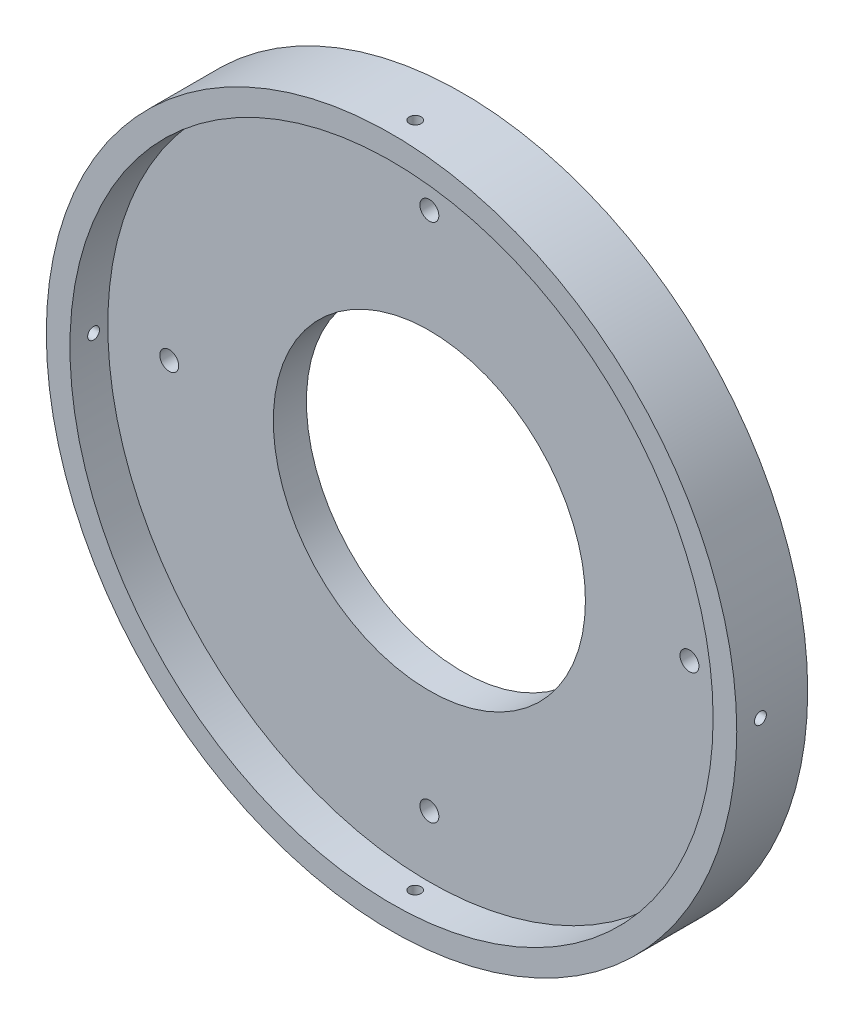
SolidWorks part; units mm, degrees
material "PET"
ref_plane "Front Plane" through (0, 0, 0) normal (0, 0, 1) x (1, 0, 0)
ref_plane "Top Plane" through (0, 0, 0) normal (0, 1, 0) x (1, 0, 0)
ref_plane "Right Plane" through (0, 0, 0) normal (1, 0, 0) x (0, 0, -1)
sketch "Sketch1" plane through (0, 0, 0) normal (0, 0, 1) x (1, 0, 0)
  circle A0 centre (0, 0) radius 73
  circle A1 centre (0, 0) radius 33
  dimension "D1" = 146
  dimension "D2" = 40
extrude "Boss-Extrude1" add sketch "Sketch1" along normal blind 7
sketch "Sketch2" plane through (0, 0, 7) normal (0, 0, 1) x (1, 0, 0)
  circle A0 centre (0, 0) radius 68
  circle A1 centre (0, 0) radius 73
  circle A2 centre (0, 0) radius 73
  dimension "D1" = 0
  dimension "D2" = 5
extrude "Boss-Extrude2" add sketch "Sketch2" along normal blind 8
sketch "Sketch3" plane through (0, 0, 0) normal (0, 1, 0) x (1, 0, 0)
  line L0 (-73, -15) -> (73, -15) construction
  circle A0 centre (0, -10) radius 1.25
  dimension "D2" = 2.5
  dimension "D1" = 5
extrude "Cut-Extrude1" cut sketch "Sketch3" against normal up to surface (73 mm away) up to face at (73, 0, 0)
pattern_circular "CirPattern1" count 4 over 360 about axis through (0, 0, 7) along (0, 0, -1) of "Cut-Extrude1"
sketch "Sketch9" plane through (0, 0, 0) normal (0, 0, -1) x (-1, 0, 0)
  point P0 (0, 55)
  point P4 (55, 0)
  point P6 (0, -55)
  point P8 (-55, 0)
  dimension "D1" = 55
  dimension "D2" = 0
  dimension "D3" = 55
  dimension "D4" = 55
  dimension "D5" = 55
hole_wizard "Ø4.0mm Dowel Hole1" positions "Sketch9" profile "Sketch10" hole size "Ø4.0" standard "ISO" end condition through all
sketch "Sketch10" plane through (0, 55, 0) normal (1, 0, 0) x (0, 1, 0)
  line L0 (0, 0) -> (0, 15)
  line L1 (0, 15) -> (2, 15)
  line L2 (2, 15) -> (2, 0)
  line L5 (2, 0) -> (0, 0)
  line L11 (0, -6.35) -> (0, 107.95) construction
  dimension "Thru Hole Dia." = 4
  dimension "Thru Hole Depth" = 15
sketch "Sketch13" plane through (0, 0, 0) normal (0, 0, -1) x (-1, 0, 0)
  line L0 (0, 0) -> (55, 0) construction
  line L1 (4.0415, 55) -> (2.0207, 58.5)
  line L2 (2.0207, 58.5) -> (-2.0207, 58.5)
  line L3 (-2.0207, 58.5) -> (-4.0415, 55)
  line L4 (-4.0415, 55) -> (-2.0207, 51.5)
  line L5 (-2.0207, 51.5) -> (2.0207, 51.5)
  line L6 (2.0207, 51.5) -> (4.0415, 55)
  line L7 (55, -4.0415) -> (58.5, -2.0207)
  line L8 (58.5, -2.0207) -> (58.5, 2.0207)
  line L9 (58.5, 2.0207) -> (55, 4.0415)
  line L10 (55, 4.0415) -> (51.5, 2.0207)
  line L11 (51.5, 2.0207) -> (51.5, -2.0207)
  line L12 (51.5, -2.0207) -> (55, -4.0415)
  line L13 (-4.0415, -55) -> (-2.0207, -58.5)
  line L14 (-2.0207, -58.5) -> (2.0207, -58.5)
  line L15 (2.0207, -58.5) -> (4.0415, -55)
  line L16 (4.0415, -55) -> (2.0207, -51.5)
  line L17 (2.0207, -51.5) -> (-2.0207, -51.5)
  line L18 (-2.0207, -51.5) -> (-4.0415, -55)
  line L19 (-55, 4.0415) -> (-58.5, 2.0207)
  line L20 (-58.5, 2.0207) -> (-58.5, -2.0207)
  line L21 (-58.5, -2.0207) -> (-55, -4.0415)
  line L22 (-55, -4.0415) -> (-51.5, -2.0207)
  line L23 (-51.5, -2.0207) -> (-51.5, 2.0207)
  line L24 (-51.5, 2.0207) -> (-55, 4.0415)
  circle A0 centre (0, 55) radius 3.5 construction
  circle A1 centre (55, 0) radius 3.5 construction
  circle A2 centre (0, -55) radius 3.5 construction
  circle A3 centre (-55, 0) radius 3.5 construction
  point P40 (0, 0)
  dimension "D1" = 7
extrude "Cut-Extrude2" cut sketch "Sketch13" against normal blind 3.2
